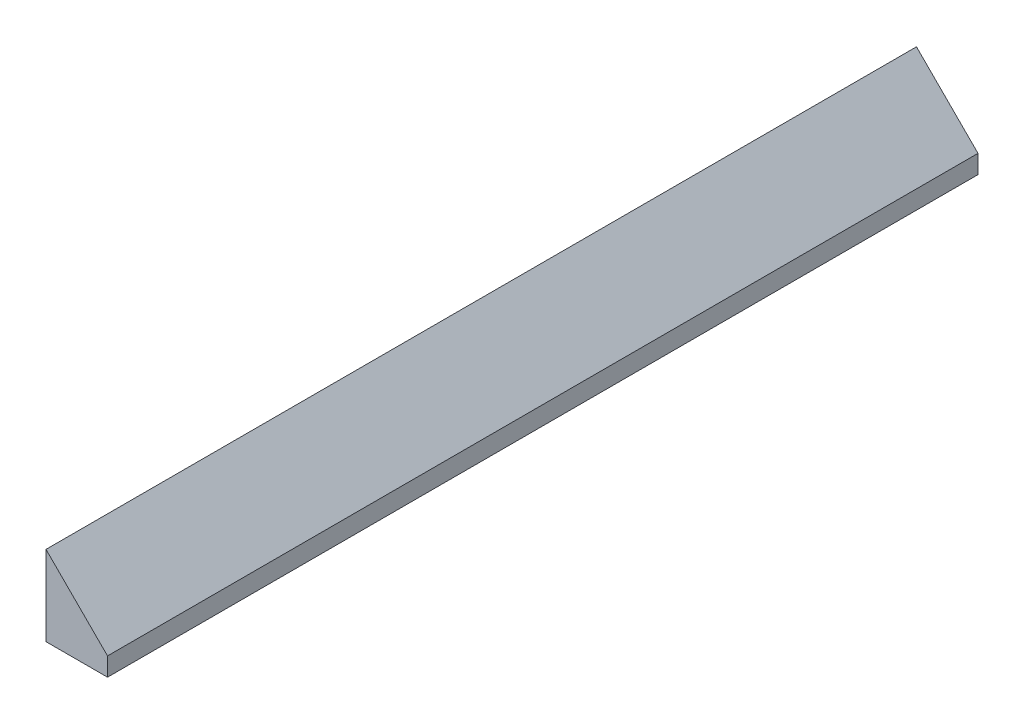
SolidWorks part; units mm, degrees
material "6061-T6 (SS)"
ref_plane "Front Plane" through (0, 0, 0) normal (0, 0, 1) x (1, 0, 0)
ref_plane "Top Plane" through (0, 0, 0) normal (0, 1, 0) x (1, 0, 0)
ref_plane "Right Plane" through (0, 0, 0) normal (1, 0, 0) x (0, 0, -1)
sketch "Sketch1" plane through (0, 0, 0) normal (0, 0, 1) x (1, 0, 0)
  line L5 (0, 0) -> (2.6, 0)
  line L6 (2.6, 0) -> (0, 2.6)
  line L7 (0, 2.6) -> (0, 0)
  line L11 (2, 0) -> (2, 0.6)
  dimension "D1" = 0.6
  dimension "D2" = 2.6
extrude "Boss-Extrude1" add sketch "Sketch1" against normal mid plane 28.3 contours L5 L11 L6 L7 region at (0.7917, 0.9042, 0)
